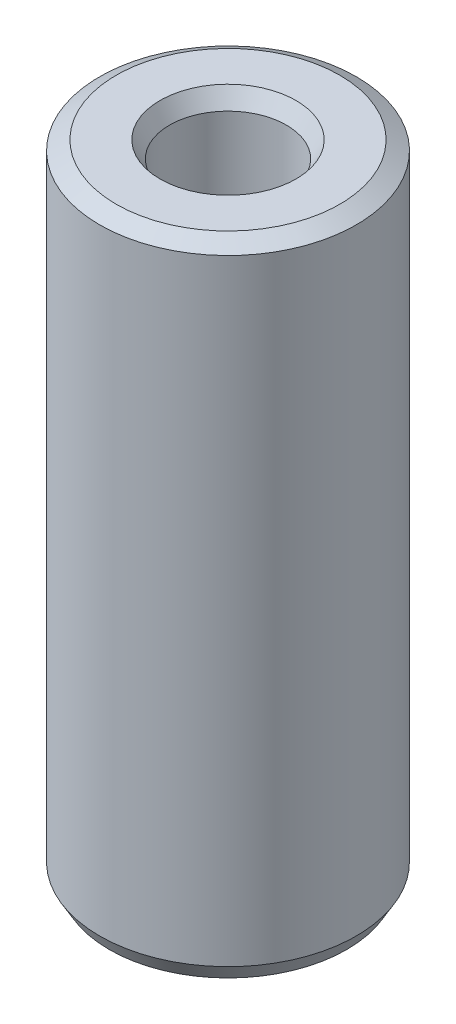
SolidWorks part; units mm, degrees
ref_plane "Front Plane" through (0, 0, 0) normal (0, 0, 1) x (1, 0, 0)
ref_plane "Top Plane" through (0, 0, 0) normal (0, 1, 0) x (1, 0, 0)
ref_plane "Right Plane" through (0, 0, 0) normal (1, 0, 0) x (0, 0, -1)
sketch "Sketch1" plane through (0, 0, 0) normal (0, 1, 0) x (1, 0, 0)
  circle A0 centre (0, 0) radius 30
  dimension "SLEEVE_OD" = 60
extrude "Boss-Extrude1" add sketch "Sketch1" along normal blind 150.0653
sketch "Sketch2" plane through (0, 0, 0) normal (0, 1, 0) x (1, 0, 0)
  circle A0 centre (0, 0) radius 13.6692
  dimension "BORE_D" = 27.3385
extrude "Cut-Extrude1" cut sketch "Sketch2" along normal through all
chamfer "Chamfer1" distance 2.2323 angle 60 4 edges at (0, 150.0653, 13.6692) (0, 0, 13.6692) (0, 0, 30) (0, 150.0653, 30) first distance on face at (0, 150.0653, 13.6692) first distance on face at (0, 0, 13.6692) first distance on face at (0, 150.0653, 30)
